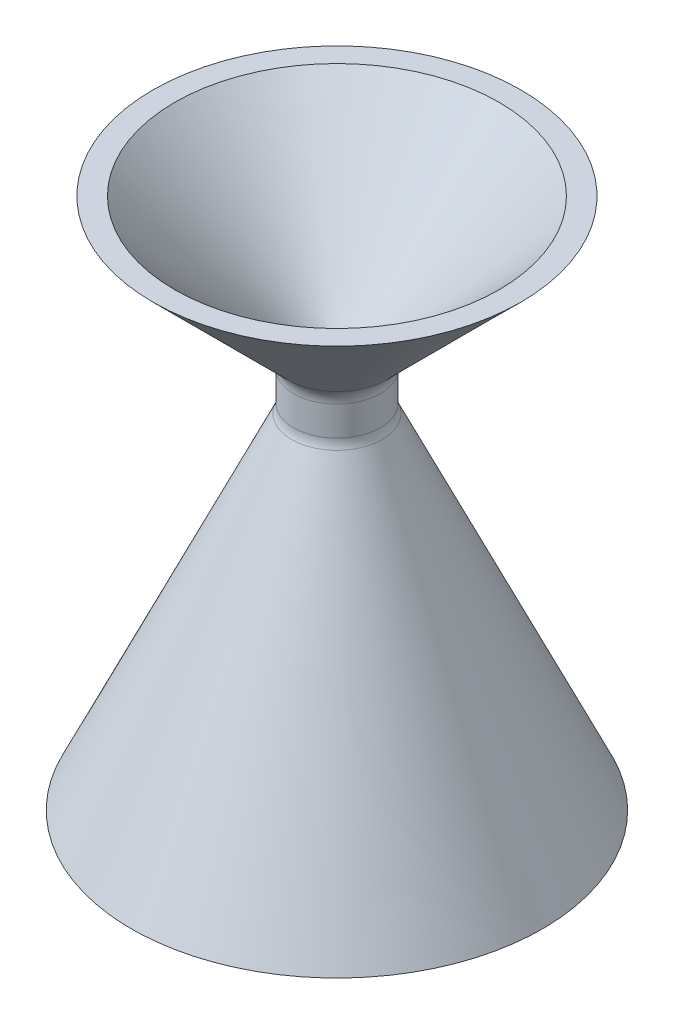
SolidWorks part; units mm, degrees
ref_plane "Front Plane" through (0, 0, 0) normal (0, 0, 1) x (1, 0, 0)
ref_plane "Top Plane" through (0, 0, 0) normal (0, 1, 0) x (1, 0, 0)
ref_plane "Right Plane" through (0, 0, 0) normal (1, 0, 0) x (0, 0, -1)
sketch "Sketch1" plane through (0, 0, 0) normal (0, 0, 1) x (1, 0, 0)
  line L0 (0, 0) -> (0, 0.0492) construction
  line L1 (0, 0) -> (0, -1.3091) construction
  line L2 (0, 0) -> (-1.899, 0) construction
  line L3 (3.175, 0.7039) -> (3.175, 5.0349)
  line L4 (3.4725, -0.6379) -> (26.9875, -51.0661)
  line L5 (26.9875, -51.0661) -> (30.1625, -51.0661)
  line L7 (6.35, 5.0349) -> (6.35, 0.7039)
  line L8 (7.2799, 7.2799) -> (26.9875, 26.9875)
  line L9 (6.6475, -0.6379) -> (30.1625, -51.0661)
  line L10 (26.9875, 26.9875) -> (23.8125, 26.9875)
  line L11 (23.8125, 26.9875) -> (4.1049, 7.2799)
  arc A0 (6.35, 5.0349) -> (7.2799, 7.2799) centre (9.525, 5.0349) cw
  arc A1 (6.6475, -0.6379) -> (6.35, 0.7039) centre (9.525, 0.7039) cw
  arc A2 (3.4725, -0.6379) -> (3.175, 0.7039) centre (6.35, 0.7039) cw
  arc A3 (3.175, 5.0349) -> (4.1049, 7.2799) centre (6.35, 5.0349) cw
  point P14 (6.35, 6.35)
  point P17 (6.35, 0)
  point P20 (3.175, 0)
  point P24 (3.175, 6.35)
  dimension "D7" = 26.9875
  dimension "D9" = 3.175
  dimension "D1" = 3.175
  dimension "D2" = 30.1625
  dimension "D3" = 6.35
  dimension "D4" = 25
  dimension "D5" = 3.175
  dimension "D6" = 0
  dimension "D8" = 45
  dimension "D10" = 51.0661
revolve "Revolve1" add sketch "Sketch1" angle 360 about L0
